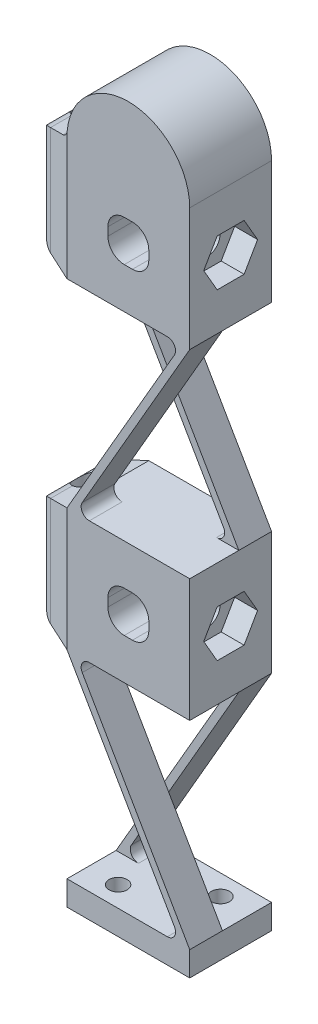
SolidWorks part; units mm, degrees
material "PET"
ref_plane "Front Plane" through (0, 0, 0) normal (0, 0, 1) x (1, 0, 0)
ref_plane "Top Plane" through (0, 0, 0) normal (0, 1, 0) x (1, 0, 0)
ref_plane "Right Plane" through (0, 0, 0) normal (1, 0, 0) x (0, 0, -1)
sketch "Sketch1" plane through (0, 0, 0) normal (0, 0, 1) x (1, 0, 0)
  line L0 (0, 0) -> (57.9688, 0) construction
  line L1 (7.5, 12.1244) -> (-7.5, 12.1244)
  line L2 (7.5, -27.1244) -> (-7.5, -27.1244)
  line L3 (7.5, -27.1244) -> (7.5, -12.1244)
  line L4 (7.5, -12.1244) -> (-7.5, -12.1244)
  line L5 (-7.5, -27.1244) -> (-7.5, -12.1244)
  line L6 (7.5, -27.1244) -> (-7.5, -12.1244) construction
  line L7 (7.5, -12.1244) -> (-7.5, -27.1244) construction
  line L8 (-7.5, 27.1244) -> (-7.5, 12.1244)
  line L9 (0, 0) -> (0, 41.5625) construction
  line L10 (7.5, 27.1244) -> (-7.5, 27.1244)
  line L11 (7.5, 27.1244) -> (7.5, 12.1244)
  line L12 (-7.5, 12.1244) -> (6.5, -12.1244)
  line L13 (6.5, -12.1244) -> (7.5, -12.1244)
  line L14 (7.5, -12.1244) -> (-6.5, 12.1244)
  line L15 (-6.5, 12.1244) -> (-7.5, 12.1244)
  line L16 (7.5, 12.1244) -> (-6.5, -12.1244)
  line L17 (-7.5, -12.1244) -> (6.5, 12.1244)
  point P1 (0, -19.6244)
  dimension "D1" = 15
  dimension "D2" = 60
extrude "Boss-Extrude1" add sketch "Sketch1" along normal mid plane 10 contours L5 L2 L3 L4 region at (0, -19.6244, 0)
extrude "cross_flexure" add sketch "Sketch1<3>" against normal blind 4 from surface contours L17 L4 L16 L12 | L17 L14 L16 L1 | L17 L12 L16 L14 region at (3.6296, 6.276, 0) region at (0, 0, 0) region at (-3.6296, -6.276, 0) starting at face at (0, -19.6244, 5)
sketch "Sketch1<3>" plane through (0, 0, 0) normal (0, 0, 1) x (1, 0, 0) same geometry as "Sketch1"
extrude "Boss-Extrude3" add sketch "Sketch1<4>" along normal blind 4 from surface contours L12 L17 L14 L1 | L14 L16 L12 L4 | L17 L12 L16 L14 region at (0, 0, 0) region at (3.6296, -6.276, 0) region at (-3.6296, 6.276, 0) starting at face at (0, -19.6244, -5)
sketch "Sketch1<4>" plane through (0, 0, 0) normal (0, 0, 1) x (1, 0, 0) same geometry as "Sketch1"
extrude "Boss-Extrude4" add sketch "Sketch1<5>" along normal mid plane 10 contours L11 L10 L8 L1 region at (0, 19.6244, 0)
sketch "Sketch1<5>" plane through (0, 0, 0) normal (0, 0, 1) x (1, 0, 0) same geometry as "Sketch1"
ref_plane "Plane1" through (0, 19.6244, 0) normal (0, -1, 0) x (-1, 0, 0)
ref_plane "Plane2" through (7.5, -27.1244, 5) normal (-1, 0, 0) x (0, 0, 1)
ref_plane "Plane3" through (0, -19.6244, 0) normal (0, 1, 0) x (1, 0, 0)
mirror "Mirror2" about plane through (0, 19.6244, 0) normal (0, -1, 0) of "cross_flexure", "Boss-Extrude3"
mirror "Mirror3" about plane through (0, 19.6244, 0) normal (0, -1, 0) of "Boss-Extrude1"
mirror "Mirror4" about plane through (0, -19.6244, 0) normal (0, 1, 0) of "cross_flexure"
mirror "Mirror5" about plane through (0, -19.6244, 0) normal (0, 1, 0) of "Boss-Extrude3"
mirror "Mirror6" about plane through (0, -19.6244, 0) normal (0, 1, 0) of "Boss-Extrude4"
sketch "Sketch29" plane through (0, 0, 5) normal (0, 0, 1) x (1, 0, 0)
  line L0 (7.5, 66.3731) -> (-7.5, 66.3731) construction
  line L1 (7.5, 66.3731) -> (-7.5, 66.3731)
  arc A0 (-7.5, 66.3731) -> (7.5, 66.3731) centre (0, 66.3731) cw
  line M10 (7.5, 66.3731) -> (-7.5, 66.3731)
extrude "Boss-Extrude5" add sketch "Sketch29" against normal up to surface (10 mm away) contours A0 M10 region at (0, 69.5562, 5) up to face at (0, 0, -5)
ref_plane "Plane4" through (0, -54.3731, 0) normal (0, 1, 0) x (1, 0, 0)
sketch "Sketch36" plane through (0, -54.3731, 0) normal (0, 1, 0) x (1, 0, 0)
  line L4 (7.5, -5) -> (7.5, 5)
  line L5 (7.5, 5) -> (-7.5, 5)
  line L6 (-7.5, 5) -> (-7.5, -5)
  line L7 (-7.5, -5) -> (7.5, -5)
  line L8 (7.5, -5) -> (7.5, 5)
  line L9 (7.5, 5) -> (-7.5, 5)
  line L10 (-7.5, 5) -> (-7.5, -5)
  line L11 (-7.5, -5) -> (7.5, -5)
  dimension "D1" = 0
extrude "Cut-Extrude1" cut sketch "Sketch36" against normal through all
fillet "Fillet1" radius 1 12 edges at (-6.5, -12.1244, 3) (6.5, -12.1244, -3) (-6.5, 12.1244, -3) (6.5, 12.1244, 3) (6.5, 51.3731, -3) (-6.5, 51.3731, 3) (6.5, 27.1244, 3) (-6.5, 27.1244, -3) (-6.5, -51.3731, -3) (6.5, -51.3731, 3) (6.5, -27.1244, -3) (-6.5, -27.1244, 3)
sketch "Sketch48" plane through (0, -51.3731, 0) normal (0, 1, 0) x (1, 0, 0)
  line L0 (0, 0) -> (-7.5, -5) construction
  line L1 (-7.5, -5) -> (7.5, -5) construction
  line L2 (0, 0) -> (-3.3333, 5) construction
  line L3 (7.5, 5) -> (-7.5, 5) construction
  circle A0 centre (-3.75, -2.5) radius 1
  circle A1 centre (3.75, 2.5) radius 1
  point P6 (-3.75, -2.5)
  point P9 (3.75, 2.5)
  dimension "D1" = 2
hole_wizard "Ø2.2 (2.2) Diameter Hole1" positions "Sketch48" profile "Sketch49" hole size "Ø2.2" standard "DIN" end condition through all
sketch "Sketch49" plane through (3.75, -51.3731, -2.5) normal (1, 0, 0) x (0, 0, 1)
  line L0 (0, 0) -> (0, 3)
  line L1 (0, 3) -> (1.1, 3)
  line L2 (1.1, 3) -> (1.1, 0)
  line L5 (1.1, 0) -> (0, 0)
  line L11 (0, -6.35) -> (0, 107.95) construction
  dimension "Thru Hole Dia." = 2.2
  dimension "Thru Hole Depth" = 3
ref_plane "Plane5" through (0, 0, 0) normal (0, 0, 1) x (1, 0, 0)
ref_plane "finger_surface" through (-12.5, 0, 0) normal (-1, 0, 0) x (0, 0, 1)
sketch "Sketch82" plane through (-12.5, 0, 0) normal (-1, 0, 0) x (0, 0, 1)
  line L0 (-3.5, 64.8731) -> (-3.5, 52.8731)
  line L1 (-3.5, 52.8731) -> (1, 52.8731)
  line L2 (1, 52.8731) -> (3.5, 52.8731)
  line L3 (3.5, 52.8731) -> (3.5, 64.8731)
  line L4 (3.5, 64.8731) -> (-3.5, 64.8731)
  line L5 (-5, 66.3731) -> (-5, 51.3731)
  line L6 (-5, 51.3731) -> (1, 51.3731)
  line L7 (1, 51.3731) -> (5, 51.3731)
  line L8 (5, 51.3731) -> (5, 66.3731)
  line L9 (5, 66.3731) -> (-5, 66.3731)
  line L10 (-5, 66.3731) -> (-5, 51.3731)
  line L11 (-5, 51.3731) -> (1, 51.3731)
  line L12 (1, 51.3731) -> (5, 51.3731)
  line L13 (5, 51.3731) -> (5, 66.3731)
  line L14 (5, 66.3731) -> (-5, 66.3731)
  dimension "D2" = 1.5
loft "Loft1" add section face at (-7.5, 57.3731, 0.2) section "Sketch82" connector at (-7.5, 66.3731, 5) connector at (-12.5, 64.8731, 3.5)
sketch "Sketch83" plane through (-12.5, 0, 0) normal (-1, 0, 0) x (0, 0, 1)
  line L0 (-3.5, 25.6244) -> (-3.5, 13.6244)
  line L1 (-3.5, 13.6244) -> (-1, 13.6244)
  line L2 (-1, 13.6244) -> (3.5, 13.6244)
  line L3 (3.5, 13.6244) -> (3.5, 25.6244)
  line L4 (3.5, 25.6244) -> (-1, 25.6244)
  line L5 (-1, 25.6244) -> (-3.5, 25.6244)
  line L6 (-5, 27.1244) -> (-5, 12.1244)
  line L7 (-5, 12.1244) -> (-1, 12.1244)
  line L8 (-1, 12.1244) -> (5, 12.1244)
  line L9 (5, 12.1244) -> (5, 27.1244)
  line L10 (5, 27.1244) -> (-1, 27.1244)
  line L11 (-1, 27.1244) -> (-5, 27.1244)
  line L12 (-5, 27.1244) -> (-5, 12.1244)
  line L13 (-5, 12.1244) -> (-1, 12.1244)
  line L14 (-1, 12.1244) -> (5, 12.1244)
  line L15 (5, 12.1244) -> (5, 27.1244)
  line L16 (5, 27.1244) -> (-1, 27.1244)
  line L17 (-1, 27.1244) -> (-5, 27.1244)
  line L18 (-5, -12.1244) -> (-5, -27.1244)
  line L19 (-5, -27.1244) -> (1, -27.1244)
  line L20 (1, -27.1244) -> (5, -27.1244)
  line L21 (5, -27.1244) -> (5, -12.1244)
  line L22 (5, -12.1244) -> (1, -12.1244)
  line L23 (1, -12.1244) -> (-5, -12.1244)
  line L24 (-5, -12.1244) -> (-5, -27.1244)
  line L25 (-5, -27.1244) -> (1, -27.1244)
  line L26 (1, -27.1244) -> (5, -27.1244)
  line L27 (5, -27.1244) -> (5, -12.1244)
  line L28 (5, -12.1244) -> (1, -12.1244)
  line L29 (1, -12.1244) -> (-5, -12.1244)
  line L30 (-3.5, -13.6244) -> (-3.5, -25.6244)
  line L31 (-3.5, -25.6244) -> (1, -25.6244)
  line L32 (1, -25.6244) -> (3.5, -25.6244)
  line L33 (3.5, -25.6244) -> (3.5, -13.6244)
  line L34 (3.5, -13.6244) -> (1, -13.6244)
  line L35 (1, -13.6244) -> (-3.5, -13.6244)
  dimension "D4" = 1.5
loft "Loft2" add section face at (-7.5, 19.6244, -0.3333) section "Sketch83" connector at (-7.5, 27.1244, 5) connector at (-12.5, 25.6244, 3.5)
sketch "Sketch84" plane through (-12.5, 0, 0) normal (-1, 0, 0) x (0, 0, 1)
  line L0 (-3.5, -13.6244) -> (-3.5, -25.6244)
  line L1 (-3.5, -25.6244) -> (1, -25.6244)
  line L2 (1, -25.6244) -> (3.5, -25.6244)
  line L3 (3.5, -25.6244) -> (3.5, -13.6244)
  line L4 (3.5, -13.6244) -> (1, -13.6244)
  line L5 (1, -13.6244) -> (-3.5, -13.6244)
  line L6 (-5, -12.1244) -> (-5, -27.1244)
  line L7 (-5, -27.1244) -> (1, -27.1244)
  line L8 (1, -27.1244) -> (5, -27.1244)
  line L9 (5, -27.1244) -> (5, -12.1244)
  line L10 (5, -12.1244) -> (1, -12.1244)
  line L11 (1, -12.1244) -> (-5, -12.1244)
  line L12 (-5, -12.1244) -> (-5, -27.1244)
  line L13 (-5, -27.1244) -> (1, -27.1244)
  line L14 (1, -27.1244) -> (5, -27.1244)
  line L15 (5, -27.1244) -> (5, -12.1244)
  line L16 (5, -12.1244) -> (1, -12.1244)
  line L17 (1, -12.1244) -> (-5, -12.1244)
  dimension "D2" = 1.5
loft "Loft3" add section face at (-7.5, -19.6244, 0.3333) section "Sketch84" connector at (-7.5, -12.1244, 5) connector at (-12.5, -13.6244, 3.5)
sketch "Sketch97" plane through (7.5, 0, 0) normal (1, 0, 0) x (0, 0, -1)
  line L0 (-5, 66.3731) -> (5, 51.3731) construction
  line L1 (5, 66.3731) -> (-5, 51.3731) construction
  line L2 (-5, 66.3731) -> (5, 66.3731) construction
  line L3 (-1.6454, 61.7231) -> (-3.2909, 58.8731)
  line L4 (-3.2909, 58.8731) -> (-1.6454, 56.0231)
  line L5 (-1.6454, 56.0231) -> (1.6454, 56.0231)
  line L6 (1.6454, 56.0231) -> (3.2909, 58.8731)
  line L7 (3.2909, 58.8731) -> (1.6454, 61.7231)
  line L8 (1.6454, 61.7231) -> (-1.6454, 61.7231)
  circle A0 centre (0, 58.8731) radius 2.85 construction
  point P8 (0, 58.8731)
  dimension "D1" = 5.7
extrude "hex_nut M3" cut sketch "Sketch97" against normal blind 2.8
sketch "Sketch98" plane through (4.7, 0, 0) normal (1, 0, 0) x (0, 0, -1)
  line L0 (-1.6454, 61.7231) -> (1.6454, 56.0231) construction
  line L1 (1.6454, 61.7231) -> (-1.6454, 56.0231) construction
  circle A0 centre (0, 58.8731) radius 1.6
  point P8 (0, 58.8731)
  dimension "D1" = 3.2
extrude "Cut-Extrude5" cut sketch "Sketch98" against normal blind 8
sketch "Sketch99" plane through (0, 0, 0) normal (0, 0, 1) x (1, 0, 0)
  line L0 (7.5, 66.3731) -> (7.5, 51.3731) construction
  line L1 (-12.5, 52.8731) -> (-12.5, 64.8731) construction
  line L2 (7.5, 66.3731) -> (7.5, 51.3731) construction
  line L3 (-12.5, 52.8731) -> (-12.5, 64.8731) construction
  line L4 (-7.5, -54.3731) -> (7.5, -54.3731) construction
  line L5 (-7.5, -54.3731) -> (7.5, -54.3731) construction
  line L6 (7.5, 58.8731) -> (-3, 58.8731)
  line L7 (-10, 51.8731) -> (-10, -54.3731)
  arc A0 (-3, 58.8731) -> (-10, 51.8731) centre (-3, 51.8731) ccw
  dimension "D2" = 7
  dimension "D1" = 5
sweep "tendon_path" cut path "Sketch99" circular profile diameter 3 parameters "D3"=3
fillet "Fillet6" radius 3 19 edges at (-7.5, 66.3731, 0) (6.1, 58.8731, -3.2909)
sketch "Sketch111" plane through (0, 0, 5) normal (0, 0, 1) x (1, 0, 0)
  line L0 (-7.5, -12.1244) -> (7.5, -12.1244)
  line L1 (-7.5, -12.1244) -> (-7.5, -27.1244)
  line L2 (-7.5, -27.1244) -> (7.5, -27.1244)
  line L3 (7.5, -23.7507) -> (7.5, -30.498) construction
  line L4 (7.5, -27.1244) -> (7.5, -12.1244) construction
  line L5 (7.5, -27.1244) -> (7.5, -12.1244)
  line L6 (17.5, -37.1244) -> (17.5, -2.1244)
  line L7 (-17.5, -2.1244) -> (17.5, -2.1244)
  line L8 (-17.5, -2.1244) -> (-17.5, -37.1244)
  line L9 (-17.5, -37.1244) -> (17.5, -37.1244)
  line L10 (-2.5, -19.1244) -> (-2.5, -20.1244)
  line L11 (-0.5, -22.1244) -> (0.5, -22.1244)
  line L12 (2.5, -20.1244) -> (2.5, -19.1244)
  line L13 (-0.5, -17.1244) -> (0.5, -17.1244)
  line L14 (-2.5, -17.1244) -> (-2.5, -22.1244) construction
  line L15 (-2.5, -22.1244) -> (2.5, -22.1244) construction
  line L16 (2.5, -22.1244) -> (2.5, -17.1244) construction
  line L17 (-2.5, -17.1244) -> (2.5, -17.1244) construction
  arc A0 (-2.5, -20.1244) -> (-0.5, -22.1244) centre (-0.5, -20.1244) ccw
  arc A1 (0.5, -22.1244) -> (2.5, -20.1244) centre (0.5, -20.1244) ccw
  arc A2 (2.5, -19.1244) -> (0.5, -17.1244) centre (0.5, -19.1244) ccw
  arc A3 (-2.5, -19.1244) -> (-0.5, -17.1244) centre (-0.5, -19.1244) cw
  dimension "D3" = 2
  dimension "D1" = 10
  dimension "D2" = 5
extrude "Cut-Extrude6" cut sketch "Sketch111" against normal up to surface (10 mm away) contours A3 L10 A0 L11 A1 L12 A2 L13 region at (0, -19.6244, 5) up to face at (-0.2264, 3.4394, -5)
pattern_linear "LPattern1" count 3 spacing 39.2487 along (0, 1, 0) of "Cut-Extrude6"
pattern_linear "hex_nuts_pattern" count 3 spacing 39.2487 along (0, -1, 0) of "hex_nut M3"
pattern_linear "LPattern3" count 3 spacing 39.2487 along (0, -1, 0) of "tendon_path"
sketch "Sketch113" plane through (0, 27.1244, 0) normal (0, 1, 0) x (1, 0, 0)
  line L0 (17.5, 15) -> (-17.3164, 15)
  line L1 (-17.3164, 15) -> (-17.3164, -15)
  line L2 (-17.3164, -15) -> (17.5, -15)
  line L3 (17.5, -15) -> (17.5, 15)
  line L4 (7.5, 5) -> (-7.3164, 5)
  line L5 (-7.3164, 5) -> (-7.3164, -5)
  line L6 (-7.3164, -5) -> (7.5, -5)
  line L7 (7.5, -5) -> (7.5, 5)
  line L8 (7.5, 5) -> (-7.3164, 5)
  line L9 (-7.3164, 5) -> (-7.3164, -5)
  line L10 (-7.3164, -5) -> (7.5, -5)
  line L11 (7.5, -5) -> (7.5, 5)
  dimension "D1" = 0
  dimension "D2" = 10
extrude "cut_top_phalange" cut sketch "Sketch113" along normal through all contours L1 L2 L3 L0
sketch "Sketch114" plane through (0, 0, 5) normal (0, 0, 1) x (1, 0, 0)
  line L0 (7.5, 27.1244) -> (-7.5, 27.1244) construction
  line L1 (7.5, 27.1244) -> (-7.5, 27.1244)
  arc A0 (-7.5, 27.1244) -> (7.5, 27.1244) centre (0, 27.1244) cw
extrude "Boss-Extrude6" add sketch "Sketch114" against normal up to surface (10 mm away) up to face at (0, 19.6244, -5)
fillet "Fillet7" radius 1 1 edges at (-7.5, 27.1244, 0)
equation "\"a\"=4"
equation "\"D1@cross_flexure\" = \"a\""
equation "\"D1@Boss-Extrude3\"= \"a\""
equation "\"d_sheath\"= 3.5'M2 threaded inserts"
equation "\"r\"= 7'radius for tendon routing"
equation "\"angle\"= 60deg'angle of cross flexures"
equation "\"side_length\"= 15mm"
equation "\"d\"= \"side_length\" + \"d1\"'for linear patterns"
equation "\"w\"= 1mm'width of the cross flexures"
equation "\"d1\"= tan ( \"angle\" ) * \"diff\"'dist between top face and bottom face of 2 consecutive fingers"
equation "\"diff\"= \"side_length\" - \"w\""
equation "\"D3@Sketch1\"=\"w\""
equation "\"D2@Sketch1\"=\"angle\""
equation "\"offset\"= 1.5'loft offset for finger surface"
equation "\"D2@Sketch82\"=\"offset\""
equation "\"D3@Sketch83\"=\"offset\""
equation "\"D4@Sketch83\"=\"offset\""
equation "\"D2@Sketch84\"=\"offset\""
equation "\"D3@LPattern1\"=\"d\""
equation "\"D2@Sketch99\"=\"r\""
equation "\"D3@hex_nuts_pattern\"=\"d\""
equation "\"D3@LPattern3\"=\"d\""
